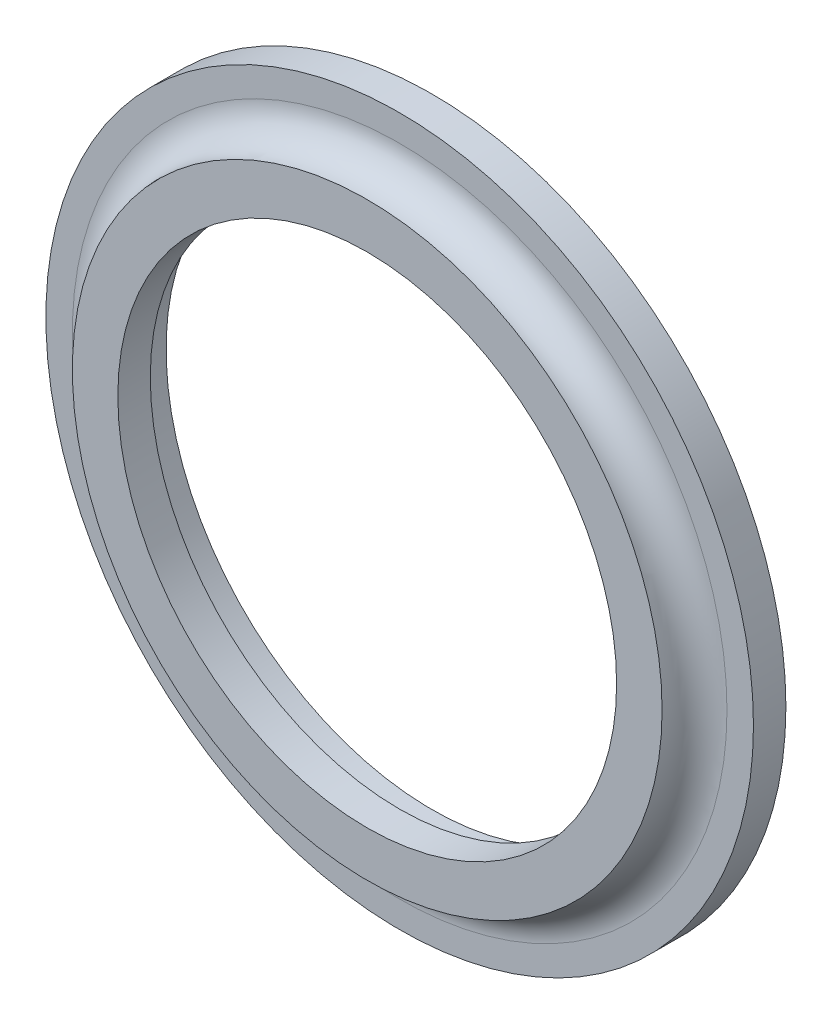
SolidWorks part; units mm, degrees
ref_plane "Front Plane" through (0, 0, 0) normal (0, 0, 1) x (1, 0, 0)
ref_plane "Top Plane" through (0, 0, 0) normal (0, 1, 0) x (1, 0, 0)
ref_plane "Right Plane" through (0, 0, 0) normal (1, 0, 0) x (0, 0, -1)
sketch "Sketch1" plane through (0, 0, 0) normal (0, 0, 1) x (1, 0, 0)
  circle A0 centre (0, 0) radius 54.5249
  circle A1 centre (0, 0) radius 41
  dimension "D1" = 82
extrude "Boss-Extrude1" add sketch "Sketch1" along normal blind 5
sketch "Sketch2" plane through (0, 0, 5) normal (0, 0, 1) x (1, 0, 0)
  circle A0 centre (0, 0) radius 45.4417
  circle A1 centre (0, 0) radius 38.4351
extrude "Boss-Extrude2" add sketch "Sketch2" along normal blind 5
fillet "Fillet1" radius 5 1 edges at (45.4417, 0, 5)
